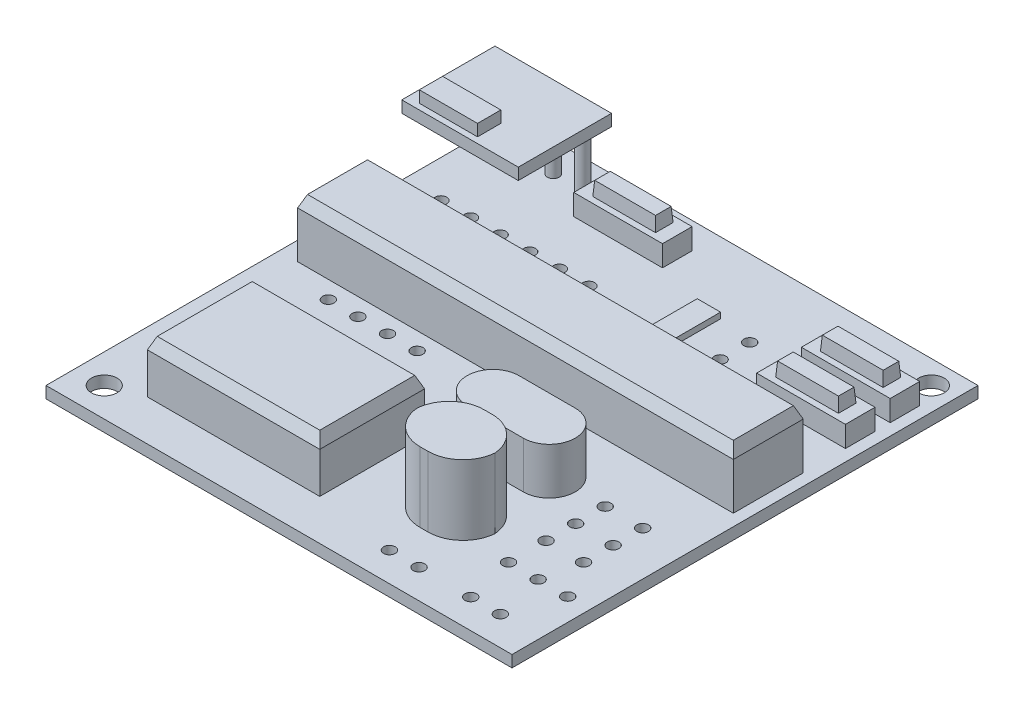
SolidWorks part; units mm, degrees
ref_plane "Ön Düzlem" through (0, 0, 0) normal (0, 0, 1) x (1, 0, 0)
ref_plane "Üst Düzlem" through (0, 0, 0) normal (0, 1, 0) x (1, 0, 0)
ref_plane "Sağ Düzlem" through (0, 0, 0) normal (1, 0, 0) x (0, 0, -1)
sketch "Sketch1" plane through (0, 0, 0) normal (0, 1, 0) x (1, 0, 0)
  line L1 (-20.7143, 17.5) -> (19.2857, 17.5)
  line L2 (-20.7143, 17.5) -> (-20.7143, -22.5)
  line L3 (-20.7143, -22.5) -> (19.2857, -22.5)
  line L4 (19.2857, 17.5) -> (19.2857, -22.5)
  dimension "D1" = 40
  dimension "D2" = 40
extrude "Boss-Extrude1" add sketch "Sketch1" along normal blind 1
sketch "Sketch2" plane through (0, 1, 0) normal (0, 1, 0) x (1, 0, 0)
  line L0 (-20.7143, 17.5) -> (-20.7143, -22.5) construction
  line L1 (-19.1143, 3.5) -> (18.2857, 3.5)
  line L2 (-19.1143, 3.5) -> (-19.1143, -2.5)
  line L3 (-19.1143, -2.5) -> (18.2857, -2.5)
  line L4 (18.2857, 3.5) -> (18.2857, -2.5)
  line L5 (-15.5143, -10) -> (-0.7143, -10)
  line L6 (-15.5143, -10) -> (-15.5143, -19)
  line L7 (-15.5143, -19) -> (-0.7143, -19)
  line L8 (-0.7143, -10) -> (-0.7143, -19)
  line L9 (-10.6143, 15.24) -> (-2.9943, 15.24)
  line L10 (-10.6143, 15.24) -> (-10.6143, 12.7)
  line L11 (-10.6143, 12.7) -> (-2.9943, 12.7)
  line L12 (-2.9943, 15.24) -> (-2.9943, 12.7)
  line L13 (10.6657, 13.5) -> (18.2857, 13.5)
  line L14 (10.6657, 13.5) -> (10.6657, 10.96)
  line L15 (10.6657, 10.96) -> (18.2857, 10.96)
  line L16 (18.2857, 13.5) -> (18.2857, 10.96)
  line L17 (10.6657, 9.66) -> (18.2857, 9.66)
  line L18 (10.6657, 9.66) -> (10.6657, 7.12)
  line L19 (10.6657, 7.12) -> (18.2857, 7.12)
  line L20 (18.2857, 9.66) -> (18.2857, 7.12)
  line L21 (2.8857, -11.5) -> (9.5857, -11.5)
  line L22 (2.8857, -11.5) -> (2.8857, -17)
  line L23 (2.8857, -17) -> (9.5857, -17)
  line L24 (9.5857, -11.5) -> (9.5857, -17)
  line L25 (19.2857, -22.5) -> (19.2857, 17.5) construction
  line L26 (19.2857, 17.5) -> (-20.7143, 17.5) construction
  line L27 (-20.7143, -22.5) -> (19.2857, -22.5) construction
  dimension "D1" = 1.6
  dimension "D2" = 1
  dimension "D3" = 14
  dimension "D4" = 20
  dimension "D5" = 5.2
  dimension "D6" = 20
  dimension "D7" = 3.5
  dimension "D8" = 9
  dimension "D9" = 9.7
  dimension "D10" = 23.6
  dimension "D11" = 5.5
  dimension "D12" = 29
  dimension "D13" = 2.54
  dimension "D14" = 4
  dimension "D15" = 1.3
  dimension "D16" = 2.54
  dimension "D17" = 7.62
  dimension "D18" = 7.62
  dimension "D19" = 7.62
  dimension "D20" = 2.54
  dimension "D21" = 1
  dimension "D22" = 2.26
  dimension "D23" = 10.1
extrude "Boss-Extrude2" add sketch "Sketch2" along normal blind 10
sketch "Sketch3" plane through (0, 11, 0) normal (0, 1, 0) x (1, 0, 0)
  line L1 (-21.551, 29.8096) -> (22.8932, 29.8096)
  line L2 (-21.551, 29.8096) -> (-21.551, 5.4044)
  line L3 (-21.551, 5.4044) -> (22.8932, 5.4044)
  line L4 (22.8932, 29.8096) -> (22.8932, 5.4044)
extrude "Cut-Extrude1" cut sketch "Sketch3" against normal blind 5
sketch "Sketch4" plane through (0, 6, 0) normal (0, 1, 0) x (1, 0, 0)
  line L1 (-17.6766, 19.0414) -> (20.3095, 19.0414)
  line L2 (-17.6766, 19.0414) -> (-17.6766, 5.5034)
  line L3 (-17.6766, 5.5034) -> (20.3095, 5.5034)
  line L4 (20.3095, 19.0414) -> (20.3095, 5.5034)
extrude "Cut-Extrude2" cut sketch "Sketch4" against normal blind 2
sketch "Sketch5" plane through (0, 4, 0) normal (0, 1, 0) x (1, 0, 0)
  line L0 (18.2857, 9.66) -> (10.6657, 9.66) construction
  line L1 (-10.6143, 15.24) -> (-2.9943, 15.24)
  line L2 (-10.6143, 15.24) -> (-10.6143, 12.7)
  line L3 (-10.6143, 12.7) -> (-2.9943, 12.7)
  line L4 (-2.9943, 15.24) -> (-2.9943, 12.7)
  line L5 (-9.4143, 14.64) -> (-4.1943, 14.64)
  line L6 (-9.4143, 14.64) -> (-9.4143, 13.3)
  line L7 (-9.4143, 13.3) -> (-4.1943, 13.3)
  line L8 (-4.1943, 14.64) -> (-4.1943, 13.3)
  line L9 (10.6657, 13.5) -> (18.2857, 13.5)
  line L10 (10.6657, 13.5) -> (10.6657, 10.96)
  line L11 (10.6657, 10.96) -> (18.2857, 10.96)
  line L12 (18.2857, 13.5) -> (18.2857, 10.96)
  line L13 (10.6657, 9.66) -> (18.2857, 9.66)
  line L14 (10.6657, 9.66) -> (10.6657, 7.12)
  line L15 (10.6657, 7.12) -> (18.2857, 7.12)
  line L16 (18.2857, 9.66) -> (18.2857, 7.12)
  line L17 (10.6657, 9.66) -> (10.6657, 7.12) construction
  line L19 (11.8657, 9.06) -> (17.0857, 9.06)
  line L20 (11.8657, 9.06) -> (11.8657, 7.72)
  line L21 (11.8657, 7.72) -> (17.0857, 7.72)
  line L22 (17.0857, 9.06) -> (17.0857, 7.72)
  line L23 (11.8657, 12.9) -> (17.0857, 12.9)
  line L24 (11.8657, 12.9) -> (11.8657, 11.56)
  line L25 (11.8657, 11.56) -> (17.0857, 11.56)
  line L26 (17.0857, 12.9) -> (17.0857, 11.56)
  dimension "D1" = 1.2
  dimension "D2" = 1.2
  dimension "D3" = 0.6
  dimension "D4" = 0.6
  dimension "D5" = 0.6
  dimension "D6" = 0.6
  dimension "D7" = 1.2
  dimension "D8" = 1.2
  dimension "D9" = 1.2
  dimension "D10" = 1.2
  dimension "D11" = 0.6
  dimension "D12" = 0.6
extrude "Cut-Extrude3" cut sketch "Sketch5" against normal blind 1.2 draft 4
sketch "Sketch6" plane through (0, 4, 0) normal (0, 1, 0) x (1, 0, 0)
  line L0 (-10.2586, 13.1177) -> (-10.2586, 14.9881)
  line L1 (-10.2586, 14.9881) -> (-3.3919, 14.9881)
  line L2 (-3.3919, 14.9881) -> (-3.3919, 12.964)
  line L3 (-3.3919, 12.964) -> (-10.2586, 13.1177)
  line L5 (11.2666, 13.1177) -> (17.5491, 13.1177)
  line L6 (11.2666, 13.1177) -> (11.2666, 11.3062)
  line L7 (11.2666, 11.3062) -> (17.5491, 11.3062)
  line L8 (17.5491, 13.1177) -> (17.5491, 11.3062)
  line L9 (11.4028, 9.3823) -> (17.5491, 9.3823)
  line L10 (11.4028, 9.3823) -> (11.4028, 7.4243)
  line L11 (11.4028, 7.4243) -> (17.5491, 7.4243)
  line L12 (17.5491, 9.3823) -> (17.5491, 7.4243)
  line L13 (23.2188, 4.5463) -> (-20.2905, 4.5463)
  line L14 (23.2188, 4.5463) -> (23.2188, 19.2032)
  line L15 (23.2188, 19.2032) -> (-20.2905, 19.2032)
  line L16 (-20.2905, 4.5463) -> (-20.2905, 19.2032)
extrude "Cut-Extrude4" cut sketch "Sketch6" against normal blind 1.2
sketch "Sketch7" plane through (0, 11, 0) normal (0, 1, 0) x (1, 0, 0)
  line L1 (-19.1143, -2.5) -> (18.2857, -2.5)
  line L2 (-19.1143, -2.5) -> (-19.1143, 3.5)
  line L3 (-19.1143, 3.5) -> (18.2857, 3.5)
  line L4 (18.2857, -2.5) -> (18.2857, 3.5)
extrude "Cut-Extrude5" cut sketch "Sketch7" against normal blind 5
chamfer "Chamfer1" distance 1 angle 23 4 edges at (-0.4143, 6, -3.5) (18.2857, 6, -0.5) (-0.4143, 6, 2.5) (-19.1143, 6, -0.5) first distance on face at (-0.4143, 3.5, -3.5) first distance on face at (18.2857, 3.5, -0.5) first distance on face at (-0.4143, 3.5, 2.5) first distance on face at (-19.1143, 3.5, -0.5)
sketch "Sketch8" plane through (0, 11, 0) normal (0, 1, 0) x (1, 0, 0)
  line L1 (-15.5143, -19) -> (-0.7143, -19)
  line L2 (-15.5143, -19) -> (-15.5143, -10)
  line L3 (-15.5143, -10) -> (-0.7143, -10)
  line L4 (-0.7143, -19) -> (-0.7143, -10)
extrude "Cut-Extrude6" cut sketch "Sketch8" against normal blind 5.5
chamfer "Chamfer2" distance 1 angle 23 4 edges at (-8.1143, 5.5, 10) (-0.7143, 5.5, 14.5) (-8.1143, 5.5, 19) (-15.5143, 5.5, 14.5) first distance on face at (-8.1143, 3.25, 10) first distance on face at (-0.7143, 3.25, 14.5) first distance on face at (-8.1143, 3.25, 19) first distance on face at (-15.5143, 3.25, 14.5)
sketch "Sketch9" plane through (0, 11, 0) normal (0, 1, 0) x (1, 0, 0)
  line L1 (2.8857, -17) -> (9.5857, -17)
  line L2 (2.8857, -17) -> (2.8857, -11.5)
  line L3 (2.8857, -11.5) -> (9.5857, -11.5)
  line L4 (9.5857, -17) -> (9.5857, -11.5)
extrude "Cut-Extrude7" cut sketch "Sketch9" against normal blind 4
fillet "Fillet1" radius 3 4 edges at (9.5857, 4, 11.5) (9.5857, 4, 17) (2.8857, 4, 17) (2.8857, 4, 11.5)
sketch "Sketch10" plane through (0, 1, 0) normal (0, 1, 0) x (1, 0, 0)
  line L0 (-20.7143, -22.5) -> (19.2857, -22.5) construction
  line L1 (-20.7143, 17.5) -> (-20.7143, -22.5) construction
  line L2 (19.2857, 17.5) -> (-20.7143, 17.5) construction
  line L3 (19.2857, -22.5) -> (19.2857, 17.5) construction
  circle A0 centre (-18.2143, -20) radius 1.1
  circle A1 centre (17.2857, 15.5) radius 1.1
  dimension "D1" = 2.5
  dimension "D2" = 2.5
  dimension "D3" = 2
  dimension "D4" = 2
extrude "Cut-Extrude8" cut sketch "Sketch10" against normal blind 4
sketch "Sketch11" plane through (0, 1, 0) normal (0, 1, 0) x (1, 0, 0)
  line L0 (-20.7143, 17.5) -> (-20.7143, -22.5) construction
  line L1 (19.2857, 17.5) -> (-20.7143, 17.5) construction
  line L2 (19.2857, -22.5) -> (19.2857, 17.5) construction
  line L3 (-20.7143, -22.5) -> (19.2857, -22.5) construction
  circle A0 centre (-17.5143, 8.2) radius 0.5
  circle A1 centre (-14.9743, 8.2) radius 0.5
  circle A2 centre (-9.8943, 8.2) radius 0.5
  circle A3 centre (-7.3543, 8.2) radius 0.5
  circle A4 centre (-4.8143, 8.2) radius 0.5
  circle A5 centre (-12.4343, 8.2) radius 0.5
  circle A9 centre (-14.9743, -4.0048) radius 0.5
  circle A10 centre (-12.4343, -4.0048) radius 0.5
  circle A11 centre (-9.8943, -4.0048) radius 0.5
  circle A12 centre (-7.3543, -4.0048) radius 0.5
  circle A13 centre (6.2857, 10.9) radius 0.5
  circle A14 centre (6.2857, 8.36) radius 0.5
  circle A15 centre (12.2857, -7.5) radius 0.5
  circle A16 centre (12.2857, -10.04) radius 0.5
  circle A17 centre (12.2857, -12.58) radius 0.5
  circle A18 centre (15.5057, -7.5) radius 0.5
  circle A19 centre (15.5057, -10.04) radius 0.5
  circle A20 centre (15.5057, -12.58) radius 0.5
  circle A21 centre (12.2857, -15.8) radius 0.5
  circle A22 centre (14.8257, -15.8) radius 0.5
  circle A23 centre (17.3657, -15.8) radius 0.5
  circle A24 centre (15.7857, -20) radius 0.5
  circle A25 centre (13.2457, -20) radius 0.5
  circle A26 centre (8.8057, -20) radius 0.5
  circle A27 centre (6.2657, -20) radius 0.5
  dimension "D1" = 3.2
  dimension "D3" = 2.54
  dimension "D8" = 6.6
  dimension "D10" = 2.54
  dimension "D11" = 7
  dimension "D13" = 2.54
  dimension "D15" = 3.22
  dimension "D16" = 3.22
  dimension "D17" = 2.54
  dimension "D19" = 2.5
  dimension "D21" = 2.54
  dimension "D22" = 4.44
  dimension "D23" = 2.54
  dimension "D2" = 9.3
  dimension "D4" = 2.54
  dimension "D5" = 2.54
  dimension "D6" = 2.54
  dimension "D7" = 2.54
  dimension "D9" = 13
  dimension "D12" = 15
  dimension "D14" = 2.54
  dimension "D18" = 2.54
  dimension "D20" = 3.5
extrude "Cut-Extrude10" cut sketch "Sketch11" against normal blind 4
sketch "Sketch12" plane through (0, 1, 0) normal (0, 1, 0) x (1, 0, 0)
  line L4 (19.2857, 17.5) -> (-20.7143, 17.5) construction
  line L5 (-20.7143, 17.5) -> (-20.7143, -22.5) construction
  circle A6 centre (-17.2143, 15) radius 0.5
  circle A7 centre (-14.6743, 15) radius 0.5
  circle A8 centre (-12.1343, 15) radius 0.5
  dimension "D1" = 2.5
  dimension "D3" = 2.54
  dimension "D2" = 3.5
  dimension "D4" = 0
  dimension "D5" = 2.54
  dimension "D6" = 0
extrude "Boss-Extrude3" add sketch "Sketch12" along normal blind 5
sketch "Sketch13" plane through (0, 6, 0) normal (0, 1, 0) x (1, 0, 0)
  line L0 (19.2857, 17.5) -> (-20.7143, 17.5) construction
  line L1 (-20.6743, 16) -> (-10.6743, 16)
  line L2 (-20.6743, 16) -> (-20.6743, 8)
  line L3 (-20.6743, 8) -> (-10.6743, 8)
  line L4 (-10.6743, 16) -> (-10.6743, 8)
  circle A0 centre (-14.6743, 15) radius 0.5 construction
  dimension "D1" = 6
  dimension "D2" = 4
  dimension "D3" = 8
  dimension "D4" = 1.5
extrude "Boss-Extrude4" add sketch "Sketch13" along normal blind 1
sketch "Sketch14" plane through (0, 7, 0) normal (0, 1, 0) x (1, 0, 0)
  line L0 (-20.6743, 16) -> (-20.6743, 8) construction
  line L1 (-19.6743, 10.5) -> (-14.6743, 10.5)
  line L2 (-19.6743, 10.5) -> (-19.6743, 8.5)
  line L3 (-19.6743, 8.5) -> (-14.6743, 8.5)
  line L4 (-14.6743, 10.5) -> (-14.6743, 8.5)
  line L5 (-20.6743, 8) -> (-10.6743, 8) construction
  dimension "D1" = 1
  dimension "D2" = 0.5
  dimension "D3" = 2
  dimension "D4" = 5
extrude "Boss-Extrude5" add sketch "Sketch14" along normal blind 1
sketch "Sketch15" plane through (0, 1, 0) normal (0, 1, 0) x (1, 0, 0)
  line L0 (2.8557, -7.7) -> (7.6857, -7.7) construction
  line L1 (2.8557, -5.47) -> (7.6857, -5.47)
  line L2 (2.8557, -9.93) -> (7.6857, -9.93)
  line L3 (19.2857, -22.5) -> (19.2857, 17.5) construction
  line L4 (-20.7143, -22.5) -> (19.2857, -22.5) construction
  arc A0 (2.8557, -5.47) -> (2.8557, -9.93) centre (2.8557, -7.7) ccw
  arc A1 (7.6857, -9.93) -> (7.6857, -5.47) centre (7.6857, -7.7) ccw
  point P2 (5.2707, -7.7)
  dimension "D1" = 11.6
  dimension "D2" = 14.8
extrude "Boss-Extrude6" add sketch "Sketch15" along normal blind 4
sketch "Sketch16" plane through (0, 1, 0) normal (0, 1, 0) x (1, 0, 0)
  line L0 (-20.7143, -22.5) -> (19.2857, -22.5) construction
  line L1 (1.2857, 11.4) -> (3.2857, 11.4)
  line L2 (1.2857, 11.4) -> (1.2857, 7.4)
  line L3 (1.2857, 7.4) -> (3.2857, 7.4)
  line L4 (3.2857, 11.4) -> (3.2857, 7.4)
  line L5 (-18.5643, -11.5) -> (-16.5643, -11.5)
  line L6 (-18.5643, -11.5) -> (-18.5643, -15.5)
  line L7 (-18.5643, -15.5) -> (-16.5643, -15.5)
  line L8 (-16.5643, -11.5) -> (-16.5643, -15.5)
  line L9 (-20.7143, 17.5) -> (-20.7143, -22.5) construction
  line L10 (19.2857, 17.5) -> (-20.7143, 17.5) construction
  line L11 (19.2857, -22.5) -> (19.2857, 17.5) construction
  dimension "D1" = 2
  dimension "D2" = 4
  dimension "D3" = 2
  dimension "D4" = 4
  dimension "D5" = 7
  dimension "D6" = 2.15
  dimension "D7" = 6.1
  dimension "D8" = 16
extrude "Boss-Extrude7" add sketch "Sketch16" along normal blind 0.5
